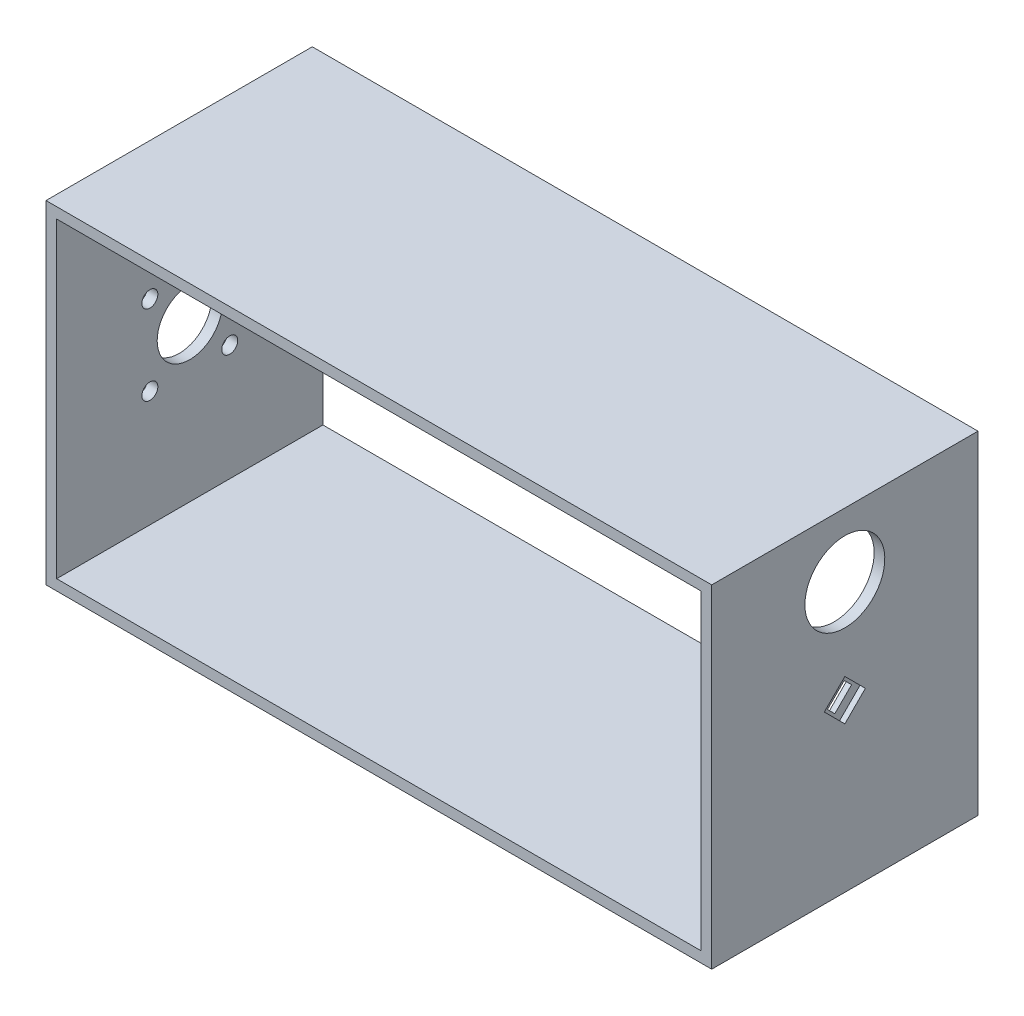
SolidWorks part; units mm, degrees
ref_plane "Ebene vorne" through (0, 0, 0) normal (0, 0, 1) x (1, 0, 0)
ref_plane "Ebene oben" through (0, 0, 0) normal (0, 1, 0) x (1, 0, 0)
ref_plane "Ebene rechts" through (0, 0, 0) normal (1, 0, 0) x (0, 0, -1)
sketch "Skizze1" plane through (0, 0, 0) normal (0, 0, 1) x (1, 0, 0)
  line L1 (0, 125) -> (250, 125)
  line L2 (0, 125) -> (0, 0)
  line L3 (0, 0) -> (250, 0)
  line L4 (250, 125) -> (250, 0)
  line L5 (246, 121) -> (4, 121)
  line L6 (246, 121) -> (246, 4)
  line L7 (246, 4) -> (4, 4)
  line L8 (4, 121) -> (4, 4)
  dimension "D1" = 250
  dimension "D2" = 125
  dimension "D3" = 4
  dimension "D4" = 4
  dimension "D5" = 4
  dimension "D6" = 4
extrude "Aufsatz-Linear austragen1" add sketch "Skizze1" along normal blind 100
sketch "Skizze2" plane through (0, 0, 0) normal (-1, 0, 0) x (0, 0, 1)
  line L0 (0, 125) -> (100, 0) construction
  circle A0 centre (50, 62.5) radius 12.25
extrude "Schnitt-Linear austragen1" cut sketch "Skizze2" against normal blind 10
sketch "Skizze3" plane through (246, 0, 0) normal (-1, 0, 0) x (0, 0, 1)
  line L0 (0, 101) -> (50, 101) construction
  line L1 (0, 4) -> (0, 121) construction
  line L2 (50, 101) -> (100, 101) construction
  line L3 (100, 4) -> (100, 121) construction
  line L4 (50, 101) -> (50, 121) construction
  line L5 (100, 121) -> (0, 121) construction
  circle A0 centre (50, 101) radius 15
extrude "Schnitt-Linear austragen2" cut sketch "Skizze3" against normal blind 10
sketch "Skizze4" plane through (0, 0, 0) normal (-1, 0, 0) x (0, 0, 1)
  line L0 (35, 77.5) -> (65, 77.5) construction
  line L1 (35, 77.5) -> (35, 47.5) construction
  line L2 (35, 47.5) -> (65, 47.5) construction
  line L3 (65, 47.5) -> (65, 77.5) construction
  line L4 (0, 125) -> (0, 0) construction
  line L5 (100, 125) -> (0, 125) construction
  circle A0 centre (35, 77.5) radius 3
  circle A1 centre (65, 77.5) radius 3
  circle A2 centre (65, 47.5) radius 3
  circle A3 centre (35, 47.5) radius 3
  dimension "D1" = 35
  dimension "D2" = 47.5
  dimension "D3" = 30
  dimension "D4" = 30
extrude "Schnitt-Linear austragen3" cut sketch "Skizze4" against normal blind 10
sketch "Skizze8" plane through (250, 0, 0) normal (1, 0, 0) x (0, 0, -1)
  line L0 (-100, 62.5) -> (0, 62.5) construction
  line L1 (-100, 0) -> (-100, 125) construction
  line L2 (0, 0) -> (0, 125) construction
  line L3 (-50, 125) -> (-50, 0) construction
  line L4 (-100, 125) -> (0, 125) construction
  line L5 (-100, 0) -> (0, 0) construction
  line L6 (-50, 70.2075) -> (-57.7075, 62.5)
  line L11 (-50, 70.2075) -> (-42.2925, 62.5)
  line L12 (-57.7075, 62.5) -> (-50, 54.7925)
  line L13 (-42.2925, 62.5) -> (-50, 54.7925)
  line L14 (-50, 70.2075) -> (-50, 54.7925) construction
  line L15 (-57.7075, 62.5) -> (-42.2925, 62.5) construction
  point P12 (0, 0)
  point P13 (-50, 62.5)
  point P14 (0, 0)
  point P15 (0, 0)
  point P20 (-50, 62.5)
  point P21 (0, 0)
  point P22 (-50, 62.5)
  point P23 (-57.3807, 67.091)
  point P24 (0, 0)
  point P25 (0, 0)
  point P26 (-55.1785, 66.7952)
  point P27 (-57.7075, 62.5)
  dimension "D1" = 10.9
  dimension "D2" = 10.9
extrude "Schnitt-Linear austragen6" cut sketch "Skizze8" against normal blind 2
sketch "Skizze10" plane through (248, 0, 0) normal (1, 0, 0) x (0, 0, -1)
  line L0 (-48.2287, 67.0219) -> (-54.5219, 60.7287)
  line L1 (-48.2287, 67.0219) -> (-45.4781, 64.2713)
  line L2 (-54.5219, 60.7287) -> (-51.7713, 57.9781)
  line L3 (-45.4781, 64.2713) -> (-51.7713, 57.9781)
  line L4 (-57.7075, 62.5) -> (-50, 54.7925) construction
  line L5 (-42.2925, 62.5) -> (-50, 70.2075) construction
  line L6 (-51.3753, 63.8753) -> (-53.8537, 66.3537) construction
  line L7 (-48.6247, 61.1247) -> (-46.1463, 58.6463) construction
  line L10 (-50, 54.7925) -> (-42.2925, 62.5) construction
  point P12 (-46.1463, 58.6463)
  point P15 (-53.8537, 66.3537)
  dimension "D1" = 3.89
  dimension "D2" = 1
  dimension "D3" = 1
extrude "Schnitt-Linear austragen8" cut sketch "Skizze10" against normal blind 32
